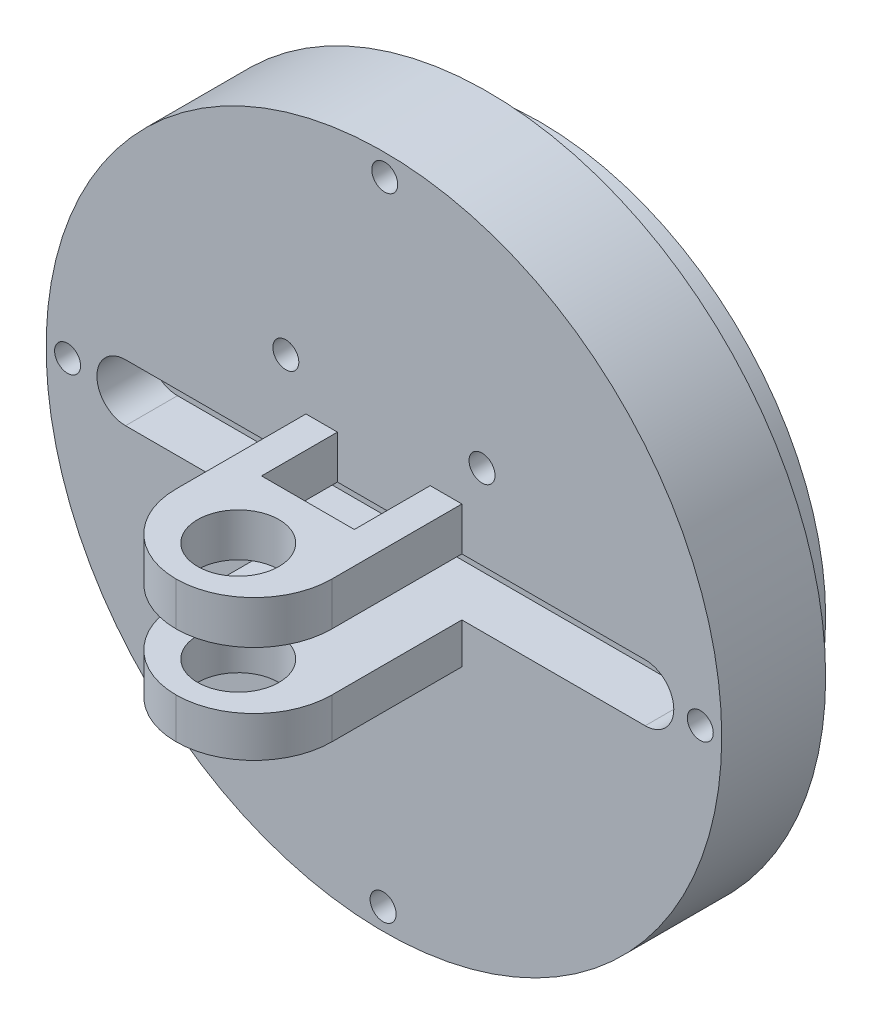
SolidWorks part; units mm, degrees
ref_plane "Front Plane" through (0, 0, 0) normal (1, 0, 0) x (0, 1, 0)
ref_plane "Top Plane" through (0, 0, 0) normal (0, 0, 1) x (0, 1, 0)
ref_plane "Right Plane" through (0, 0, 0) normal (0, 1, 0) x (-1, 0, 0)
sketch "Sketch2" plane through (0, 0, 0) normal (0, 0, 1) x (0, 1, 0)
  circle A0 centre (0, 0) radius 65
  dimension "D1" = 130
extrude "Boss-Extrude1" add sketch "Sketch2" along normal blind 20
sketch "Sketch4" plane through (0, 0, 0) normal (0, 0, -1) x (1, 0, 0)
  circle A0 centre (0, 0) radius 55
  dimension "D1" = 110
extrude "Boss-Extrude2" add sketch "Sketch4" along normal blind 10
shell "Shell1" thickness 20 removed face at (-55, 0, -10)
sketch "Sketch11" plane through (0, 0, -10) normal (0, 0, -1) x (1, 0, 0)
  line L0 (-0.1429, 45.1514) -> (2.153, 45.1514)
  line L1 (2.153, 45.1514) -> (6.3791, 34.4138)
  line L2 (6.3791, 34.4138) -> (-6.6667, 34.3592)
  line L3 (-6.6667, 34.3592) -> (-2.847, 45.1514)
  line L4 (-2.847, 45.1514) -> (-0.1429, 45.1514)
  circle A1 centre (0, 0) radius 35 construction
  circle A2 centre (0, 0) radius 35 construction
extrude "Cut-Extrude4" cut sketch "Sketch11" against normal blind 10
pattern_circular "CirPattern3" count 12 over 360 about axis through (0, 0, -10) along (0, 0, 1) of "Cut-Extrude4"
sketch "Sketch12" plane through (0, 0, 20) normal (0, 0, 1) x (1, 0, 0)
  line L0 (-49.7242, 0) -> (50.2758, 0) construction
  line L1 (-49.7242, 5.5) -> (50.2758, 5.5)
  line L2 (-49.7242, -5.5) -> (50.2758, -5.5)
  arc A0 (-49.7242, 5.5) -> (-49.7242, -5.5) centre (-49.7242, 0) ccw
  arc A1 (50.2758, -5.5) -> (50.2758, 5.5) centre (50.2758, 0) ccw
  point P3 (0.2758, 0)
  dimension "D1" = 11
  dimension "D2" = 100
extrude "Cut-Extrude5" cut sketch "Sketch12" against normal blind 10
sketch "Sketch13" plane through (0, 0, 20) normal (0, 0, 1) x (1, 0, 0)
  circle A0 centre (0.1587, 60.8709) radius 2.5
  dimension "D1" = 5
extrude "Cut-Extrude7" cut sketch "Sketch13" against normal blind 10 contours A0
pattern_circular "CirPattern4" count 4 over 360 about axis through (0, 0, 20) along (0, 0, -1) of "Cut-Extrude7"
sketch "Sketch14" plane through (0, 0, 20) normal (0, 0, 1) x (1, 0, 0)
  line L0 (50.2758, 5.5) -> (-49.7242, 5.5) construction
  line L1 (-15, 13.8216) -> (15, 13.8216)
  line L2 (-15, 13.8216) -> (-15, 5.5)
  line L3 (-15, 5.5) -> (15, 5.5)
  line L4 (15, 13.8216) -> (15, 5.5)
  line L5 (-49.7242, -5.5) -> (50.2758, -5.5) construction
  line L6 (-15, -5.5) -> (15, -5.5)
  line L7 (-15, -5.5) -> (-15, -13.316)
  line L8 (-15, -13.316) -> (15, -13.316)
  line L9 (15, -5.5) -> (15, -13.316)
  dimension "D1" = 15
  dimension "D2" = 15
  dimension "D3" = 15
  dimension "D4" = 15
extrude "Boss-Extrude3" add sketch "Sketch14" along normal blind 40
sketch "Sketch15" plane through (0, -13.316, 0) normal (0, -1, 0) x (1, 0, 0)
  circle A0 centre (0, 48.0248) radius 7.825
  dimension "D1" = 15.65
extrude "Cut-Extrude8" cut sketch "Sketch15" against normal blind 60
fillet "Fillet3" radius 15 4 edges at (-15, -9.408, 60) (-15, 9.6608, 60) (15, 9.6608, 60) (15, -9.408, 60)
sketch "Sketch16" plane through (0, 13.8216, 0) normal (0, 1, 0) x (-1, 0, 0)
  line L0 (-15, 20) -> (15, 20) construction
  line L1 (-8.9056, 20) -> (8.9451, 20)
  line L2 (-8.9056, 20) -> (-8.9056, 34.6029)
  line L3 (-8.9056, 34.6029) -> (8.9451, 34.6029)
  line L4 (8.9451, 20) -> (8.9451, 34.6029)
extrude "Cut-Extrude9" cut sketch "Sketch16" against normal blind 10
sketch "Sketch19" plane through (0, 0, 20) normal (0, 0, 1) x (1, 0, 0)
  circle A0 centre (-18.8783, 21.7438) radius 2.5
  circle A1 centre (18.8783, 21.7438) radius 2.5
  dimension "D1" = 5
extrude "Cut-Extrude10" cut sketch "Sketch19" against normal blind 10
